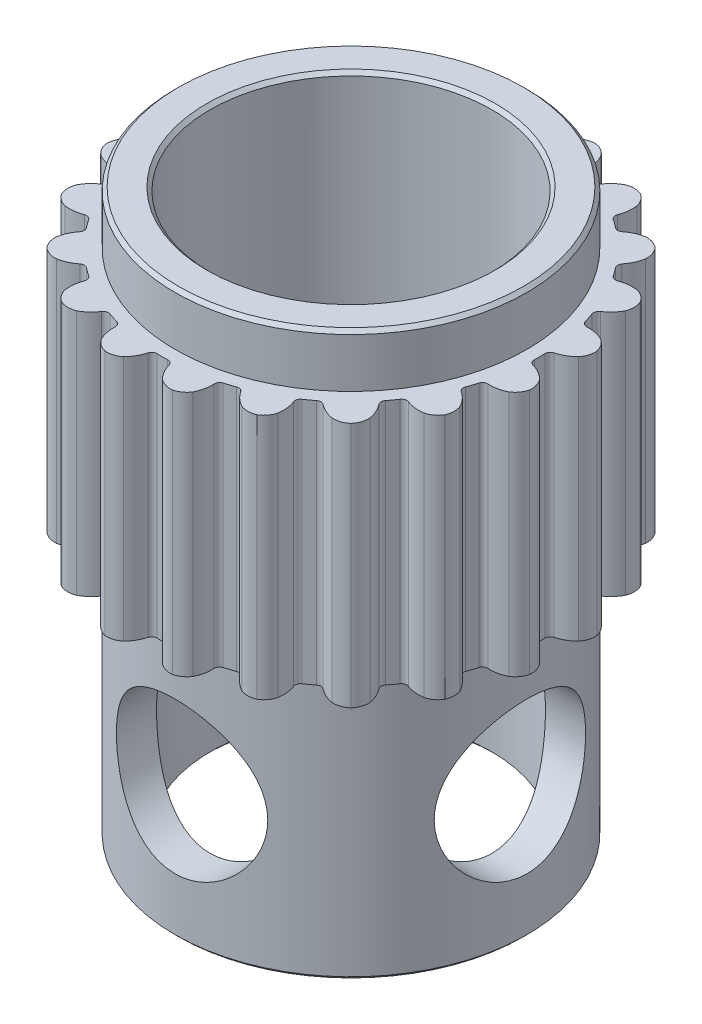
SolidWorks part; units mm, degrees
material "6061-T6 (SS)"
ref_plane "Front Plane" through (0, 0, 0) normal (0, 0, 1) x (1, 0, 0)
ref_plane "Top Plane" through (0, 0, 0) normal (0, 1, 0) x (1, 0, 0)
ref_plane "Right Plane" through (0, 0, 0) normal (1, 0, 0) x (0, 0, -1)
sketch "Body Sketch" plane through (0, 0, 0) normal (0, 0, 1) x (1, 0, 0)
  line L0 (6.11, -3.5) -> (6.11, 3.5)
  line L3 (6.11, 3.5) -> (4, 3.5)
  line L4 (4, 3.5) -> (4, -3.5)
  line L9 (4, -3.5) -> (6.11, -3.5)
  line L12 (0, 0) -> (6.11, 0) construction
  line L13 (0, 3.5) -> (0, -3.5) construction
  dimension "BoreDia" = 8
  dimension "Height" = 7
  dimension "RefBeltPathDia" = 12.22
revolve "Body" add sketch "Body Sketch" angle 360 about L13
sketch "GT2 Profile Sketch" plane through (0, 0, 0) normal (0, 1, 0) x (1, 0, 0)
  line L1 (0, -6.11) -> (0, -5.36) construction
  line L2 (-0.9955, -6.0283) -> (-0.8733, -5.2884) construction
  line L3 (0, 0) -> (-0.8733, -5.2884) construction
  line L4 (0.9955, -6.0283) -> (0, 0) construction
  arc A3 (0.2997, -5.4688) -> (0.1507, -5.3579) centre (0.1549, -5.5078) ccw
  arc A4 (-0.9955, -6.0283) -> (0.9955, -6.0283) centre (0, 0) ccw
  arc A5 (-0.2997, -5.4688) -> (-0.1507, -5.3579) centre (-0.1549, -5.5078) cw
  arc A6 (-0.2997, -5.4688) -> (-0.5497, -5.907) centre (-1.2653, -5.2085) cw
  arc A8 (-0.1507, -5.3579) -> (0.1507, -5.3579) centre (0, 0) ccw
  arc A9 (-0.5497, -5.907) -> (-0.9955, -6.0283) centre (-0.9051, -5.4808) cw
  arc A10 (0.2997, -5.4688) -> (0.5497, -5.907) centre (1.2653, -5.2085) ccw
  arc A11 (0.5497, -5.907) -> (0.9955, -6.0283) centre (0.9051, -5.4808) ccw
  circle A12 centre (0, 0) radius 5.36 construction
  circle A13 centre (0, 0) radius 6.11 construction
  dimension "BottomRadius" = 0.15
  dimension "MidRadius" = 1
  dimension "TopRadius" = 0.555
  dimension "Height" = 0.75
  dimension "XDistMidRadius" = 0.4
  dimension "ArcLengthAngle" = 18.755
  dimension "ArcLength" = 2
extrude "GT2 Profile" cut sketch "GT2 Profile Sketch" along direction (0, -1, 0) on the side against the normal up to next (3.5 mm away) and the other way up to next (3.5 mm away)
pattern_circular "GT2 Circular Pattern" count 20 over 360 about axis through (0, 3.5, 0) along (0, 1, 0) of "GT2 Profile"
sketch "Top Wall Sketch" plane through (0, 3.5, 0) normal (0, 1, 0) x (1, 0, 0)
  circle A0 centre (0, 0) radius 4 construction
  circle A1 centre (0, 0) radius 4
  circle A2 centre (0, 0) radius 5
  dimension "Thickness" = 1
extrude "Top Wall" add sketch "Top Wall Sketch" along normal blind 1.5
sketch "BottomWallS" plane through (0, -3.5, 0) normal (0, -1, 0) x (-1, 0, 0)
  circle A0 centre (0, 0) radius 4
  circle A1 centre (0, 0) radius 4 construction
  circle A2 centre (0, 0) radius 5
  circle A3 centre (0, 0) radius 5 construction
extrude "Bottom Wall" add sketch "BottomWallS" along normal blind 7.5
ref_plane "Clearance Hole Plane" through (0, 0, 5) normal (0, 0, 1) x (1, 0, 0)
hole_wizard "Set Screw Clearance Hole" positions "Sketch1" profile "Sketch2" hole size "M4" standard "ANSI Metric" end condition up to next
sketch "Sketch1" plane through (0, 0, 5) normal (0, 0, 1) x (1, 0, 0)
  line L0 (0, -11) -> (0, -3.5) construction
  line L1 (-5, -11) -> (5, -11) construction
  line L2 (-0.1507, -3.5) -> (0.1507, -3.5) construction
  point P0 (0, -7.25)
sketch "Sketch2" plane through (0, -7.25, 5) normal (1, 0, 0) x (0, -1, 0)
  line L0 (0, 0) -> (0, 1)
  line L1 (0, 1) -> (2.15, 1)
  line L2 (2.15, 1) -> (2.15, 0)
  line L5 (2.15, 0) -> (0, 0)
  line L11 (0, -6.35) -> (0, 107.95) construction
  dimension "Thru Hole Dia." = 4.3
  dimension "Thru Hole Depth" = 1
pattern_circular "Set Screw Hole Pattern" count 2 every 90 about axis through (0, -11, 0) along (0, 1, 0) of "Set Screw Clearance Hole"
chamfer "Inner Chamfer" distance 0.1 angle 45 2 edges at (0, 5, 4) (0, -11, -4)
chamfer "Outer Chamfer" distance 0.1 angle 45 2 edges at (0, -11, -5) (0, 5, 5)
equation "\"D1@GT2 Circular Pattern\" = int ( 360 / \"ArcLengthAngle@GT2 Profile Sketch\" )  + 1"
